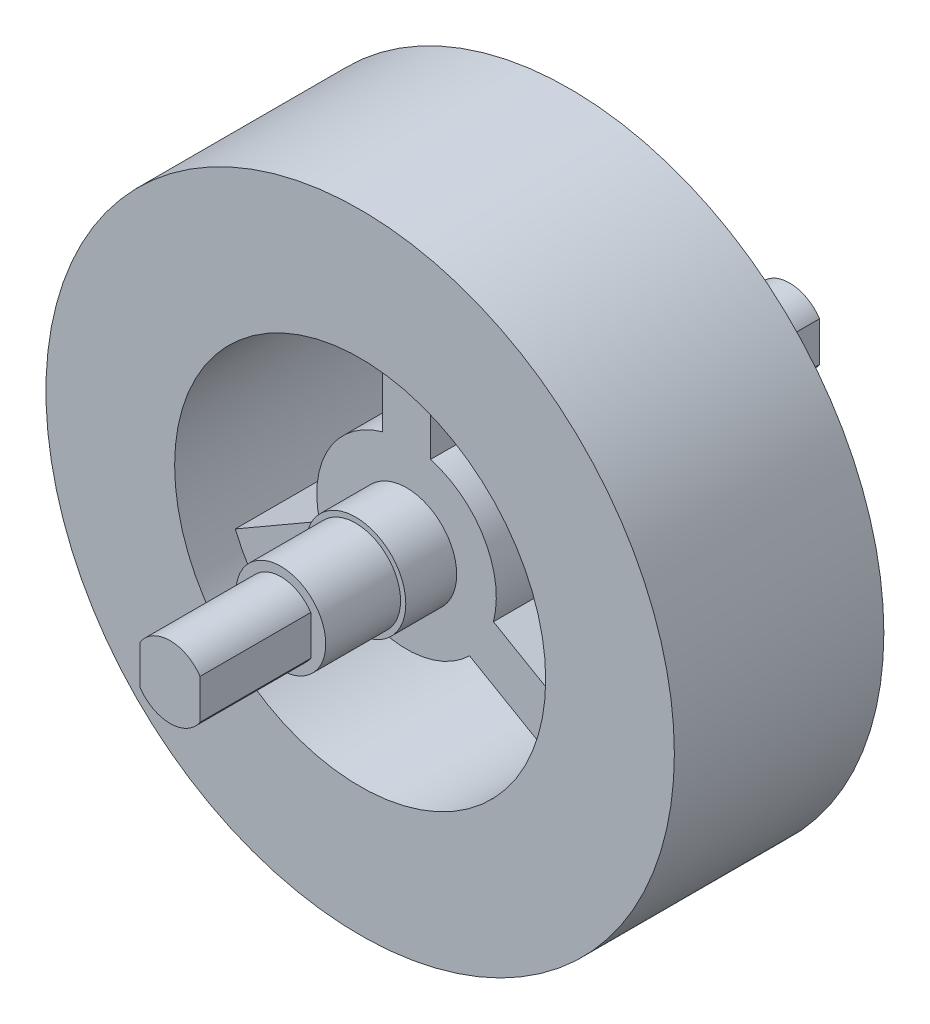
SolidWorks part; units mm, degrees
material "Copper"
ref_plane "Front Plane" through (0, 0, 0) normal (0, 0, 1) x (1, 0, 0)
ref_plane "Top Plane" through (0, 0, 0) normal (0, 1, 0) x (1, 0, 0)
ref_plane "Right Plane" through (0, 0, 0) normal (1, 0, 0) x (0, 0, -1)
sketch "Sketch1" plane through (0, 0, 0) normal (0, 0, 1) x (1, 0, 0)
  circle A0 centre (0, 0) radius 7.5
  dimension "D1" = 15
extrude "Boss-Extrude1" add sketch "Sketch1" along normal blind 30.75 and the other way blind 35.75 contours A0
sketch "Sketch3" plane through (0, 0, 0) normal (0, 0, 1) x (1, 0, 0)
  line L0 (5, 3.3166) -> (5, -3.3166)
  line L1 (-5, 3.3166) -> (-5, -3.3166)
  arc A0 (5, 3.3166) -> (-5, 3.3166) centre (0, 0) ccw
  arc A1 (-5, -3.3166) -> (5, -3.3166) centre (0, 0) ccw
  point P7 (0, 0)
  point P8 (0, 0)
  dimension "D1" = 12
  dimension "D2" = 10
extrude "Boss-Extrude3" add sketch "Sketch3" along normal blind 49.25 and the other way blind 54.25
sketch "Sketch4" plane through (0, 0, 0) normal (0, 0, 1) x (1, 0, 0)
  circle A0 centre (0, 0) radius 52.5
  circle A1 centre (0, 0) radius 31
  dimension "D1" = 105
  dimension "D2" = 62
extrude "Boss-Extrude4" add sketch "Sketch4" along normal mid plane 35
sketch "Sketch5" plane through (0, 0, 0) normal (0, 0, 1) x (1, 0, 0)
  line L0 (14.52, -3.7643) -> (10.52, -10.6925)
  line L1 (-4, 14.4568) -> (4, 14.4568)
  line L2 (-4, 14.4568) -> (-4, 31)
  line L3 (-4, 31) -> (4, 31)
  line L4 (4, 14.4568) -> (4, 31)
  line L5 (14.52, -3.7643) -> (28.8468, -12.0359)
  line L6 (28.8468, -12.0359) -> (24.8468, -18.9641)
  line L7 (10.52, -10.6925) -> (24.8468, -18.9641)
  line L8 (-10.52, -10.6925) -> (-14.52, -3.7643)
  line L9 (-10.52, -10.6925) -> (-24.8468, -18.9641)
  line L10 (-24.8468, -18.9641) -> (-28.8468, -12.0359)
  line L11 (-14.52, -3.7643) -> (-28.8468, -12.0359)
  line L12 (0, 0) -> (4, 14.4568) construction
  circle A0 centre (0, 0) radius 15
  circle A1 centre (0, 0) radius 31 construction
  dimension "D1" = 30
  dimension "D2" = 8
  dimension "D3" = 3
extrude "Boss-Extrude5" add sketch "Sketch5" against normal offset from surface 11.25 and the other way offset from surface 7.75 contours L1 A0 L8 L0 | A0 L4 L3 L2 | A0 L7 L6 L5 | A0 L11 L10 L9 | L8 A0 | L0 A0 | L1 A0 | L2 L1 L4 L3 region at (12.7084, -7.3372, 0) region at (19.8401, -11.4547, 0) region at (0, 0, 0) region at (-12.7084, -7.3372, 0) region at (-19.8401, -11.4547, 0) region at (0, 22.9093, 0) region at (0, 14.6744, 0) up to face at (52.5, 0, -17.5) other way up to face at (52.5, 0, 17.5)
sketch "Sketch6" plane through (0, 0, -6.25) normal (0, 0, 1) x (1, 0, 0)
  circle A0 centre (0, 0) radius 9.25
  dimension "D1" = 18.5
extrude "Boss-Extrude6" add sketch "Sketch6" against normal blind 17
sketch "Sketch8" plane through (0, 0, -54.25) normal (0, 0, -1) x (-1, 0, 0)
  circle A0 centre (0, 0) radius 3
  dimension "D1" = 6
extrude "Cut-Extrude2" cut sketch "Sketch8" against normal up to surface (54.25 mm away) up to plane "Front Plane"
sketch "Sketch9" plane through (0, 0, 9.75) normal (0, 0, 1) x (1, 0, 0)
  circle A0 centre (0, 0) radius 8.375
  dimension "D1" = 16.75
extrude "Boss-Extrude7" add sketch "Sketch9" along normal blind 8.5
